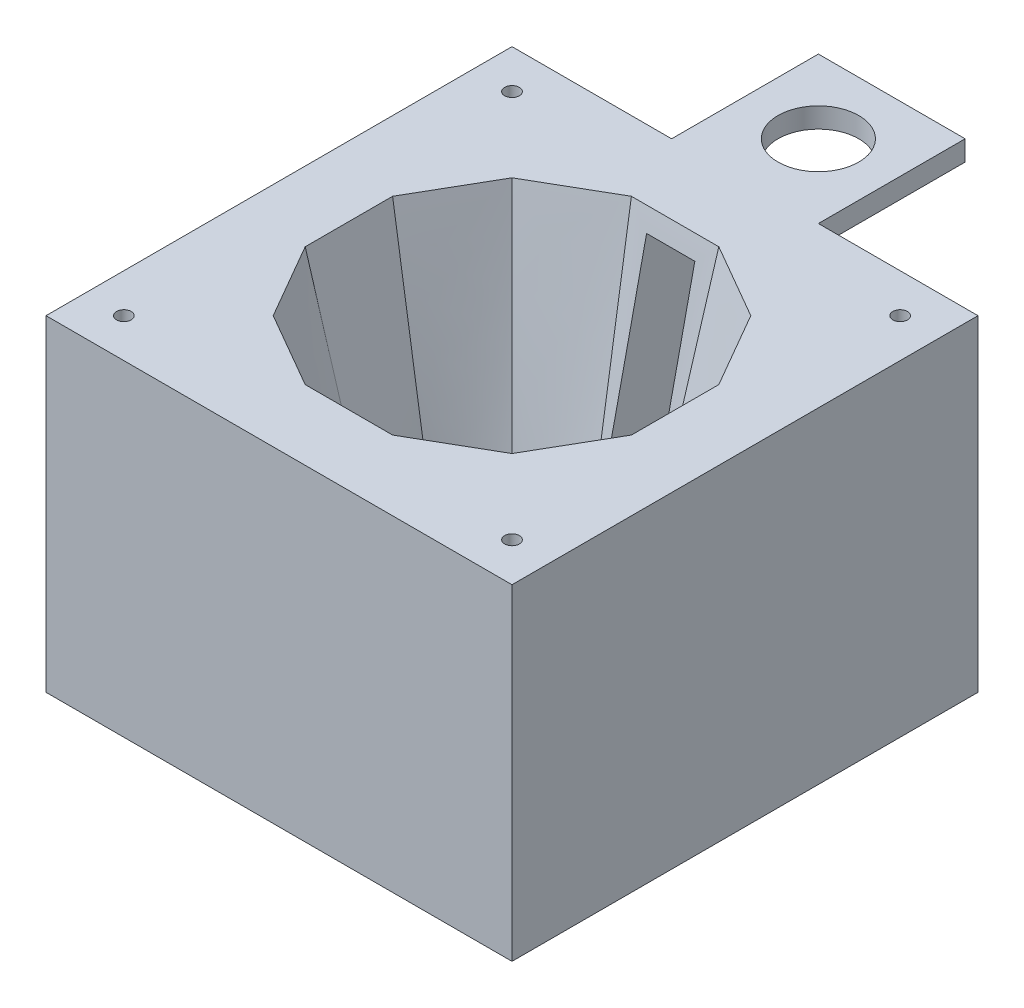
SolidWorks part; units mm, degrees
material "Nylon 101"
ref_plane "Front Plane" through (0, 0, 0) normal (0, 0, 1) x (1, 0, 0)
ref_plane "Top Plane" through (0, 0, 0) normal (0, 1, 0) x (1, 0, 0)
ref_plane "Right Plane" through (0, 0, 0) normal (1, 0, 0) x (0, 0, -1)
sketch "id" plane through (0, 0, 0) normal (0, 1, 0) x (1, 0, 0)
  circle A0 centre (0, 0) radius 25.4
  dimension "D1" = 50.8
ref_plane "Outside face" through (0, 88.9, 0) normal (0, 1, 0) x (1, 0, 0)
sketch "od" plane through (0, 88.9, 0) normal (0, 1, 0) x (1, 0, 0)
  line L1 (44.45, -11.9103) -> (44.45, 11.9103)
  line L2 (44.45, 11.9103) -> (32.5397, 32.5397)
  line L3 (32.5397, 32.5397) -> (11.9103, 44.45)
  line L4 (11.9103, 44.45) -> (-11.9103, 44.45)
  line L5 (-11.9103, 44.45) -> (-32.5397, 32.5397)
  line L6 (-32.5397, 32.5397) -> (-44.45, 11.9103)
  line L7 (-44.45, 11.9103) -> (-44.45, -11.9103)
  line L8 (-44.45, -11.9103) -> (-32.5397, -32.5397)
  line L9 (-32.5397, -32.5397) -> (-11.9103, -44.45)
  line L10 (-11.9103, -44.45) -> (11.9103, -44.45)
  line L11 (11.9103, -44.45) -> (32.5397, -32.5397)
  line L12 (32.5397, -32.5397) -> (44.45, -11.9103)
  circle A0 centre (0, 0) radius 44.45 construction
  dimension "D1" = 88.9
sketch "Sketch3" plane through (0, 88.9, 0) normal (0, 1, 0) x (1, 0, 0)
  line L0 (-48.895, 0) -> (48.895, 0) construction
  line L1 (-63.5, -63.5) -> (63.5, -63.5)
  line L2 (-63.5, -63.5) -> (-63.5, 63.5)
  line L3 (-63.5, 63.5) -> (63.5, 63.5)
  line L4 (63.5, -63.5) -> (63.5, 63.5)
  line L5 (-63.5, -63.5) -> (63.5, 63.5) construction
  line L6 (-63.5, 63.5) -> (63.5, -63.5) construction
  line L7 (0, -48.895) -> (0, 48.895) construction
  circle A0 centre (-52.8934, 52.8934) radius 2
  circle A1 centre (-52.8934, -52.8934) radius 2
  circle A2 centre (52.8934, -52.8934) radius 2
  circle A3 centre (52.8934, 52.8934) radius 2
  point P0 (0, 0)
  dimension "D2" = 4
  dimension "D1" = 127
  dimension "D3" = 15
extrude "Boss-Extrude1" add sketch "Sketch3" against normal up to surface (88.9 mm away) contours L1 L4 L3 L2 A1 A0 A2 A3 | A1 | A2 | A3 | A0 region at (0, 88.9, 0) region at (-52.8934, 88.9, -52.8934) region at (-52.8934, 88.9, 52.8934) region at (52.8934, 88.9, 52.8934) region at (52.8934, 88.9, -52.8934) up to plane "Top Plane"
extrude "Cut-Extrude1" cut sketch "Sketch3<3>" against normal blind 30 contours A1 | A2 | A3 | A0 region at (-52.8934, 88.9, -52.8934) region at (-52.8934, 88.9, 52.8934) region at (52.8934, 88.9, 52.8934) region at (52.8934, 88.9, -52.8934)
sketch "Sketch3<3>" plane through (0, 88.9, 0) normal (0, 1, 0) x (1, 0, 0) same geometry as "Sketch3"
loft "Cut-Loft1" cut profiles "od", "id" connector at (-32.5397, 88.9, 32.5397) connector at (-6.8408, 0, 24.4615)
sketch "Sketch5" plane through (0, 88.9, 0) normal (0, 1, 0) x (1, 0, 0)
  line L0 (-63.5, 63.5) -> (63.5, 63.5) construction
  line L1 (-6.574, 63.5) -> (6.574, 63.5)
  line L2 (-6.574, 63.5) -> (-6.574, 24.5345)
  line L4 (6.574, 63.5) -> (6.574, 24.5345)
  arc A0 (6.574, 24.5345) -> (-6.574, 24.5345) centre (0, 0) ccw construction
  arc A1 (6.574, 24.5345) -> (-6.574, 24.5345) centre (0, 0) ccw
extrude "Cut-Extrude3" cut sketch "Sketch5" against normal offset from surface (77.9 mm away) 5.5 from offset 5.5 up to face at (0, 0, 0) offset against normal yes
sketch "Sketch6" plane through (0, 88.9, 0) normal (0, 1, 0) x (1, 0, 0)
  line L0 (-63.5, 63.5) -> (63.5, 63.5) construction
  line L1 (-20, 63.5) -> (20, 63.5)
  line L2 (-20, 63.5) -> (-20, 103.5)
  line L3 (-20, 103.5) -> (20, 103.5)
  line L4 (20, 63.5) -> (20, 103.5)
  circle A0 centre (0, 83.5) radius 11
  point P9 (0, 103.5)
  point P13 (-20, 83.5)
  dimension "D1" = 22
  dimension "D2" = 40
extrude "Boss-Extrude2" add sketch "Sketch6" against normal up to surface (5.5 mm away) up to face at (0, 83.4, -53.3813)
extrude "Boss-Extrude3" add sketch "Sketch6<2>" along normal blind 5.5 from surface starting at face at (0, 0, 0)
sketch "Sketch6<2>" plane through (0, 88.9, 0) normal (0, 1, 0) x (1, 0, 0) same geometry as "Sketch6"
equation "\"id\"= 2in"
equation "\"od\"= 4in"
equation "\"h\"= 3.5in"
equation "\"D1@id\" = \"id\""
equation "\"D1@od\" = \"h\""
